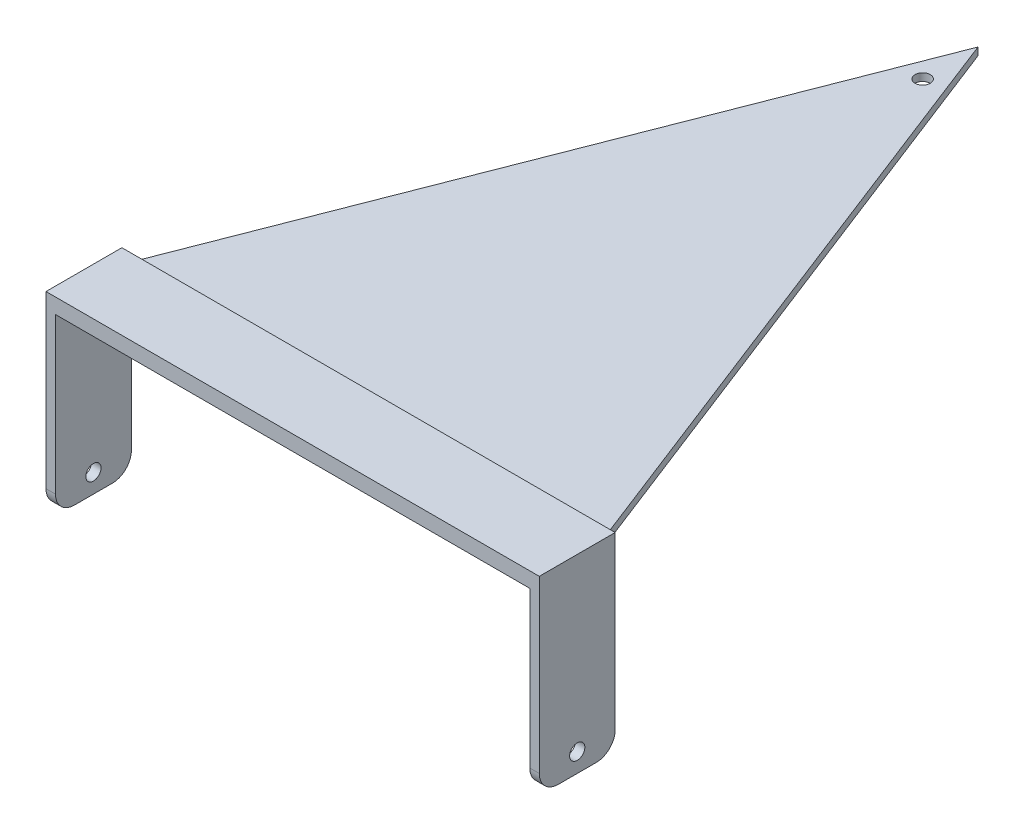
SolidWorks part; units mm, degrees
ref_plane "Front Plane" through (0, 0, 0) normal (0, 0, 1) x (1, 0, 0)
ref_plane "Top Plane" through (0, 0, 0) normal (0, 1, 0) x (1, 0, 0)
ref_plane "Right Plane" through (0, 0, 0) normal (1, 0, 0) x (0, 0, -1)
sketch "Sketch2" plane through (0, 0, 0) normal (0, 1, 0) x (1, 0, 0)
  line L3 (62.5, 179.2193) -> (62.5, 26.7241) construction
  line L4 (125, 0) -> (125, 10)
  line L5 (125, 10) -> (62.5, 170.6168)
  line L6 (125, 0) -> (125, -10)
  line L7 (125, -10) -> (0, -10)
  line L8 (0, -10) -> (0, 0)
  line L9 (0, 10) -> (62.5, 170.6168)
  line L10 (0, 0) -> (0, 10)
  line L11 (0, 0) -> (125, 0) construction
  circle A0 centre (62.5, 156.0248) radius 2
  point P3 (62.5, 156.0248)
  point P13 (130, 0)
  point P16 (-5, 0)
  dimension "D5" = 10
  dimension "D1" = 125
  dimension "D2" = 170
  dimension "D3" = 5
  dimension "D4" = 62.5
  dimension "D6" = 10
  dimension "D7" = 10
  dimension "D8" = 10
  dimension "D9" = 5
  dimension "D10" = 170
extrude "Boss-Extrude1" add sketch "Sketch2" along normal blind 2
sketch "Sketch4" plane through (0, 2, 0) normal (0, 1, 0) x (1, 0, 0)
  line L1 (0, 10) -> (125, 10)
  line L2 (0, 10) -> (0, -10)
  line L3 (0, -10) -> (125, -10)
  line L4 (125, 10) -> (125, -10)
  line L5 (125, 10) -> (127, 10)
  line L6 (125, 10) -> (125, -10)
  line L7 (125, -10) -> (127, -10)
  line L8 (127, 10) -> (127, -10)
  line L9 (0, 10) -> (-2, 10)
  line L10 (0, 10) -> (0, -10)
  line L11 (0, -10) -> (-2, -10)
  line L12 (-2, 10) -> (-2, -10)
  line M3 (0, 10) -> (0, -10)
  line M4 (0, -10) -> (125, -10)
  line M5 (125, -10) -> (125, 10)
  dimension "D1" = 2
  dimension "D2" = 2
extrude "Boss-Extrude4" add sketch "Sketch4" along normal blind 2 contours L1 M3 M4 M5 region at (62.5, 2, 0)
sketch "Sketch7" plane through (0, 4, 0) normal (0, 1, 0) x (1, 0, 0)
  line L1 (0, 10) -> (-2.5, 10)
  line L2 (0, 10) -> (0, -10)
  line L3 (0, -10) -> (-2.5, -10)
  line L4 (-2.5, 10) -> (-2.5, -10)
  line L5 (125, 10) -> (127.5, 10)
  line L6 (125, 10) -> (125, -10)
  line L7 (125, -10) -> (127.5, -10)
  line L8 (127.5, 10) -> (127.5, -10)
  dimension "D1" = 2.5
  dimension "D2" = 2.5
  dimension "D3" = 20
  dimension "D4" = 20
extrude "Boss-Extrude5" add sketch "Sketch7" against normal blind 50
fillet "Fillet1" radius 5 4 edges at (126.25, -46, 10) (126.25, -46, -10) (-1.25, -46, -10) (-1.25, -46, 10)
sketch "Sketch9" plane through (-2.5, 0, 0) normal (-1, 0, 0) x (0, 0, 1)
  line L0 (10, -41) -> (10, 4) construction
  line L1 (-5, -46) -> (5, -46) construction
  circle A0 centre (0, -41) radius 2
  dimension "D1" = 4
  dimension "D2" = 10
  dimension "D3" = 5
extrude "Cut-Extrude1" cut sketch "Sketch9" against normal blind 250
equation "\"R\"= 150"
equation "\"d\"= 20"
